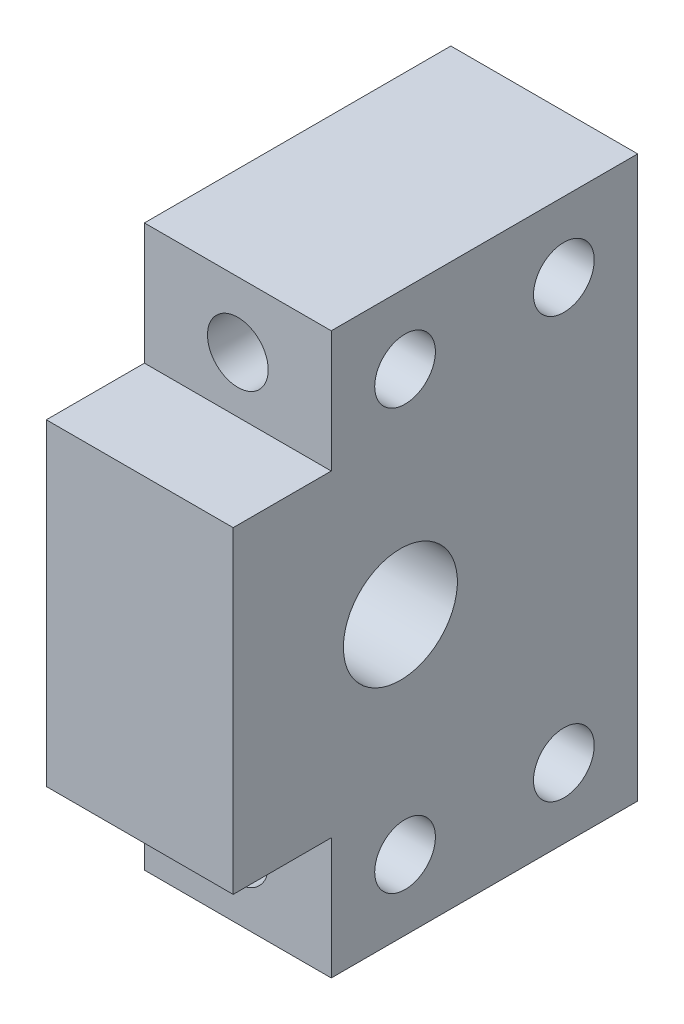
SolidWorks part; units mm, degrees
ref_plane "Front Plane" through (0, 0, 0) normal (0, 0, 1) x (1, 0, 0)
ref_plane "Top Plane" through (0, 0, 0) normal (0, 1, 0) x (1, 0, 0)
ref_plane "Right Plane" through (0, 0, 0) normal (1, 0, 0) x (0, 0, -1)
sketch "Sketch1" plane through (0, 0, 0) normal (0, 0, 1) x (1, 0, 0)
  line L0 (-285.275, 23) -> (-285.275, -23) construction
  line L1 (-295.275, 30) -> (-257.175, 30) construction
  line L2 (-295.275, -30) -> (-275.275, -30)
  line L3 (-295.275, -30) -> (-295.275, 30)
  line L4 (-295.275, 30) -> (-275.275, 30)
  line L5 (-275.275, -30) -> (-275.275, 30)
  line L6 (-295.275, -30) -> (-275.275, 30) construction
  line L7 (-295.275, 30) -> (-275.275, -30) construction
  line L10 (-295.275, -17) -> (-275.275, -17)
  line L11 (-295.275, -17) -> (-295.275, 17)
  line L12 (-295.275, 17) -> (-275.275, 17)
  line L13 (-275.275, -17) -> (-275.275, 17)
  line L14 (-295.275, -17) -> (-275.275, 17) construction
  line L15 (-295.275, 17) -> (-275.275, -17) construction
  circle A0 centre (-285.275, -23) radius 2.1 construction
  circle A1 centre (-285.275, 23) radius 2.1 construction
  circle A2 centre (-285.275, -23) radius 2.1 construction
  circle A3 centre (-285.275, 23) radius 2.1 construction
  circle A4 centre (-285.275, 23) radius 3.25
  circle A5 centre (-285.275, -23) radius 3.25
  point P10 (-285.275, 0)
  point P11 (-285.275, 0)
  point P18 (-285.275, 0)
  dimension "D1" = 6.5
  dimension "D2" = 20
  dimension "D3" = 34
extrude "Boss-Extrude1" add sketch "Sketch1" along normal blind 32.8 contours L3 L12 L5 L4 A4 | L12 L3 L10 L5 | L10 L3 L2 L5 A5 region at (-295.0365, -23.5, 0) region at (-285.275, 0, 0) region at (-295.0365, 23.5, 0)
extrude "Boss-Extrude2" add sketch "Sketch1<3>" along normal blind 10.5 from surface contours L12 L3 L10 L5 region at (-285.275, 0, 0) starting at face at (-282.025, 23, 32.8)
sketch "Sketch1<3>" plane through (0, 0, 0) normal (0, 0, 1) x (1, 0, 0) same geometry as "Sketch1"
sketch "Sketch2" plane through (0, 0, 0) normal (1, 0, 0) x (0, 0, -1)
  line L34 (0, -30) -> (0, 30)
  line L35 (0, 30) -> (-32.8, 30)
  line L36 (-32.8, 30) -> (-32.8, 17)
  line L37 (-32.8, 17) -> (-43.3, 17)
  line L38 (-43.3, 17) -> (-43.3, -17)
  line L39 (-43.3, -17) -> (-32.8, -17)
  line L40 (-32.8, -17) -> (-32.8, -30)
  line L41 (-32.8, -30) -> (0, -30)
  line L42 (0, -30) -> (0, 30)
  line L43 (0, 30) -> (-32.8, 30)
  line L44 (-32.8, 30) -> (-32.8, 17)
  line L45 (-32.8, 17) -> (-43.3, 17)
  line L46 (-43.3, 17) -> (-43.3, -17)
  line L47 (-43.3, -17) -> (-32.8, -17)
  line L48 (-32.8, -17) -> (-32.8, -30)
  line L49 (-32.8, -30) -> (0, -30)
  circle A0 centre (-25.4, 0) radius 6.1 construction
  circle A1 centre (-7.9, -22.5) radius 3.25 construction
  circle A2 centre (-24.9, -22.5) radius 3.25 construction
  circle A3 centre (-24.9, 22.5) radius 3.25 construction
  circle A4 centre (-7.9, 22.5) radius 3.25 construction
  circle A5 centre (-25.4, 0) radius 6.1
  circle A6 centre (-7.9, -22.5) radius 3.25
  circle A7 centre (-24.9, -22.5) radius 3.25
  circle A8 centre (-24.9, 22.5) radius 3.25
  circle A9 centre (-7.9, 22.5) radius 3.25
  dimension "D1" = 0
extrude "Cut-Extrude1" cut sketch "Sketch2" against normal up to surface (295.275 mm away) flip side to cut up to face at (-295.275, 0, 27.225)
